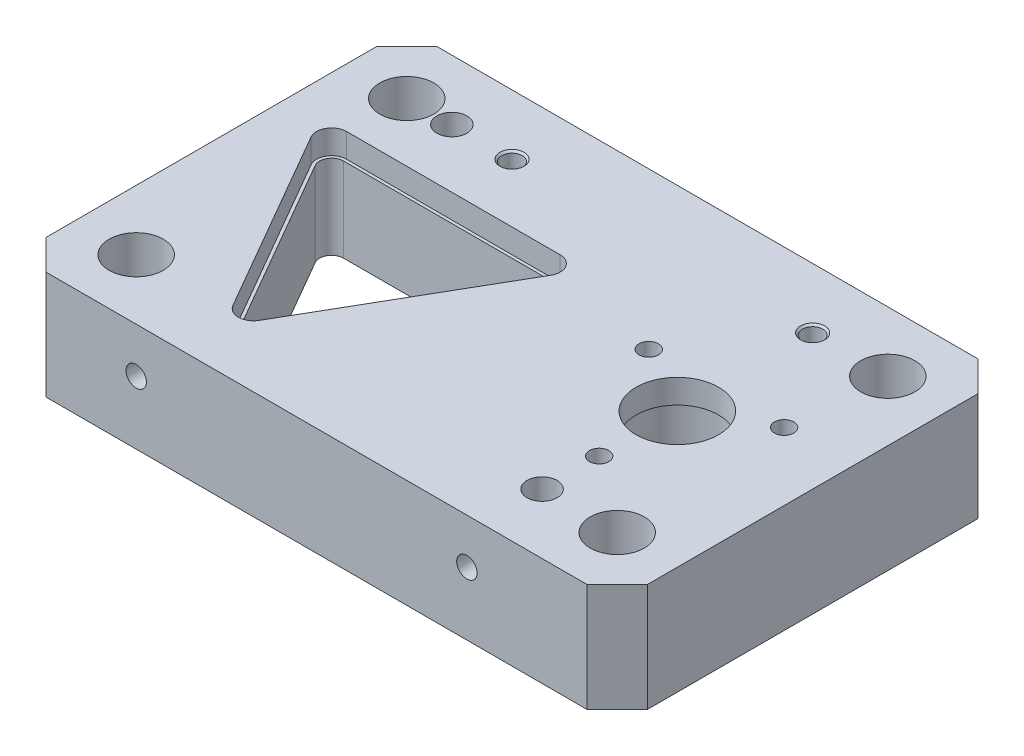
SolidWorks part; units mm, degrees
ref_plane "Front Plane" through (0, 0, 0) normal (0, 0, 1) x (1, 0, 0)
ref_plane "Top Plane" through (0, 0, 0) normal (0, 1, 0) x (1, 0, 0)
ref_plane "Right Plane" through (0, 0, 0) normal (1, 0, 0) x (0, 0, -1)
sketch "Sketch1" plane through (0, 0, 0) normal (0, 1, 0) x (1, 0, 0)
  line L0 (100, -55) -> (90, -65)
  line L1 (90, -65) -> (-90, -65)
  line L2 (100, -55) -> (100, 55)
  line L3 (90, 65) -> (-90, 65)
  line L4 (-100, -55) -> (-100, 55)
  line L5 (100, -65) -> (-100, 65) construction
  line L6 (100, 65) -> (-100, -65) construction
  line L7 (-90, -65) -> (-100, -55)
  line L8 (-90, 65) -> (-100, 55)
  line L9 (100, 55) -> (90, 65)
  line L10 (0, 0) -> (0, 65) construction
  line L11 (0, 0) -> (100, 0) construction
  line L12 (55, 26) -> (55, 0) construction
  line L13 (-40.6699, -43.5) -> (-5.1628, 18)
  line L14 (-9.493, 25.5) -> (-80.507, 25.5)
  line L15 (-84.8372, 18) -> (-49.3301, -43.5)
  line L16 (55, 0) -> (77.5167, 13) construction
  line L17 (80, -45) -> (55, -45) construction
  line L18 (-9.493, 24.5) -> (-80.507, 24.5)
  line L19 (-83.9711, 18.5) -> (-48.4641, -43)
  line L20 (-41.5359, -43) -> (-6.0289, 18.5)
  circle A0 centre (-80, 45) radius 9
  circle A1 centre (-80, 45) radius 5.5
  circle A2 centre (80, 45) radius 9
  circle A3 centre (80, 45) radius 5.5
  circle A4 centre (80, -45) radius 5.5
  circle A5 centre (80, -45) radius 9
  circle A6 centre (-80, -45) radius 9
  circle A7 centre (-80, -45) radius 5.5
  circle A8 centre (55, 0) radius 26 construction
  circle A9 centre (-45, 0) radius 25.5 construction
  arc A10 (-40.6699, -43.5) -> (-49.3301, -43.5) centre (-45, -41) cw
  arc A11 (-5.1628, 18) -> (-9.493, 25.5) centre (-9.493, 20.5) ccw
  arc A12 (-80.507, 25.5) -> (-84.8372, 18) centre (-80.507, 20.5) ccw
  circle A13 centre (55, 0) radius 14.5
  circle A14 centre (55, 0) radius 13.72
  circle A15 centre (77.5167, 13) radius 4
  circle A16 centre (77.5167, 13) radius 3.22
  circle A17 centre (55, -26) radius 3.22
  circle A18 centre (55, -26) radius 4
  circle A19 centre (32.4833, 13) radius 3.22
  circle A20 centre (32.4833, 13) radius 4
  circle A21 centre (55, -45) radius 5
  circle A22 centre (-65, 45) radius 5
  arc A23 (-80.507, 24.5) -> (-83.9711, 18.5) centre (-80.507, 20.5) ccw
  arc A24 (-41.5359, -43) -> (-48.4641, -43) centre (-45, -41) cw
  arc A25 (-6.0289, 18.5) -> (-9.493, 24.5) centre (-9.493, 20.5) ccw
  point P0 (0, 0)
  point P32 (-45, 45)
  point P57 (0, 0)
  point P69 (55, 45)
  point P70 (0, 0)
  point P71 (0, 0)
  dimension "D11" = 18
  dimension "D12" = 11
  dimension "D13" = 160
  dimension "D14" = 90
  dimension "D16" = 52
  dimension "D18" = 5
  dimension "D21" = 29
  dimension "D22" = 27.44
  dimension "D24" = 8
  dimension "D25" = 6.44
  dimension "D27" = 10
  dimension "D28" = 10
  dimension "D29" = 120
  dimension "D1" = 130
  dimension "D2" = 200
  dimension "D3" = 10
  dimension "D4" = 45
  dimension "D5" = 10
  dimension "D6" = 45
  dimension "D7" = 10
  dimension "D8" = 45
  dimension "D9" = 10
  dimension "D10" = 45
  dimension "D15" = 100
  dimension "D17" = 25.5
  dimension "D19" = 100
  dimension "D20" = 55
  dimension "D23" = 60
  dimension "D31" = 100
  dimension "D30" = 1
  dimension "D26" = 3
extrude "Boss-Extrude1" add sketch "Sketch1" against normal blind 36 contours L2 L9 L3 L8 L4 L7 L1 L0 A22 A21 A20 A18 A15 A13 A12 L14 A11 L13 A10 L15 A2 A0 A5 A6 | L14 A12 L15 A10 L13 A11 A25 L20 A24 L19 A23 L18 | A13 A14 | A20 A19 | A15 A16 | A18 A17 | A5 A4 | A2 A3 | A0 A1 | A6 A7 region at (5.1692, 0, 0) region at (-45, 0, 45.8919) region at (-88.7454, 0, -45) region at (71.2546, 0, -45) region at (71.2546, 0, 45) region at (-88.7454, 0, 45) region at (40.9101, 0, 0) region at (73.6298, 0, -13) region at (51.1131, 0, 26) region at (28.5965, 0, -13)
sketch "Sketch5" plane through (0, 0, 0) normal (0, 1, 0) x (1, 0, 0)
  point P0 (-45, 45)
  point P4 (55, 45)
hole_wizard "M8 Tapped Hole2" positions "Sketch5" profile "Sketch4" tap size "M8" standard "ISO" end condition through all
sketch "Sketch4" plane through (-45, 0, -45) normal (1, 0, 0) x (0, 0, 1)
  line L0 (0, 0) -> (0, 36)
  line L1 (0, 36) -> (3.4, 36)
  line L2 (3.4, 36) -> (3.4, 0.625)
  line L3 (3.4, 0.625) -> (4.025, 0)
  line L5 (4.025, 0) -> (0, 0)
  line L6 (-3.4, 0.625) -> (-4.025, 0) construction
  line L11 (0, -6.35) -> (0, 107.95) construction
  dimension "Thru Tap Drill Dia." = 6.8
  dimension "Thru Tap Drill Depth" = 36
  dimension "Near C'Sink Dia." = 8.05
  dimension "Near C'Sink Angle" = 90
extrude "Cut-Extrude1" cut sketch "Sketch1<3>" against normal blind 8 contours L14 A12 L15 A10 L13 A11 A25 L20 A24 L19 A23 L18 region at (-45, 0, 45.8919)
sketch "Sketch1<3>" plane through (0, 0, 0) normal (0, 1, 0) x (1, 0, 0) same geometry as "Sketch1"
extrude "Cut-Extrude2" cut sketch "Sketch1<4>" against normal blind 16 contours A0 A1 | A2 A3 | A5 A4 | A6 A7 region at (-88.7454, 0, -45) region at (71.2546, 0, -45) region at (71.2546, 0, 45) region at (-88.7454, 0, 45)
sketch "Sketch1<4>" plane through (0, 0, 0) normal (0, 1, 0) x (1, 0, 0) same geometry as "Sketch1"
extrude "Cut-Extrude3" cut sketch "Sketch1<5>" against normal through all from offset 8 contours A15 A16 | A20 A19 | A18 A17 | A14 | A13 A14 region at (40.9101, 0, 0) region at (55, 0, 0) region at (73.6298, 0, -13) region at (51.1131, 0, 26) region at (28.5965, 0, -13) offset against normal yes
sketch "Sketch1<5>" plane through (0, 0, 0) normal (0, 1, 0) x (1, 0, 0) same geometry as "Sketch1"
sketch "Sketch6" plane through (0, 0, 65) normal (0, 0, 1) x (1, 0, 0)
  line L0 (0, 0) -> (0, -36) construction
  line L1 (90, -36) -> (-90, -36) construction
  line L2 (90, 0) -> (-90, 0) construction
  line L5 (-100, -36) -> (-100, 0) construction
  point P0 (-60, -15)
  point P1 (50, -15)
  point P7 (0, 0)
  point P8 (0, 0)
  point P14 (0, 0)
  dimension "D1" = 40
  dimension "D2" = 110
  dimension "D3" = 15
sketch "Sketch9" plane through (0, 0, 65) normal (0, 0, 1) x (1, 0, 0)
  point P0 (-60, -15)
  point P3 (50, -15)
hole_wizard "M8 Tapped Hole1" positions "Sketch9" profile "Sketch10" tap size "M8" standard "ISO"
sketch "Sketch10" plane through (-60, -15, 65) normal (1, 0, 0) x (0, -1, 0)
  line L0 (0, 0) -> (0, 15)
  line L1 (0, 15) -> (3.4, 12.9571)
  line L2 (3.4, 12.9571) -> (3.4, 0)
  line L5 (3.4, 0) -> (0, 0)
  line L10 (0, 15) -> (-3.4, 12.9571) construction
  line L11 (0, -6.35) -> (0, 107.95) construction
  dimension "Tap Drill Dia." = 6.8
  dimension "Tap Drill Depth" = 15
  dimension "Drill Angle" = 118
